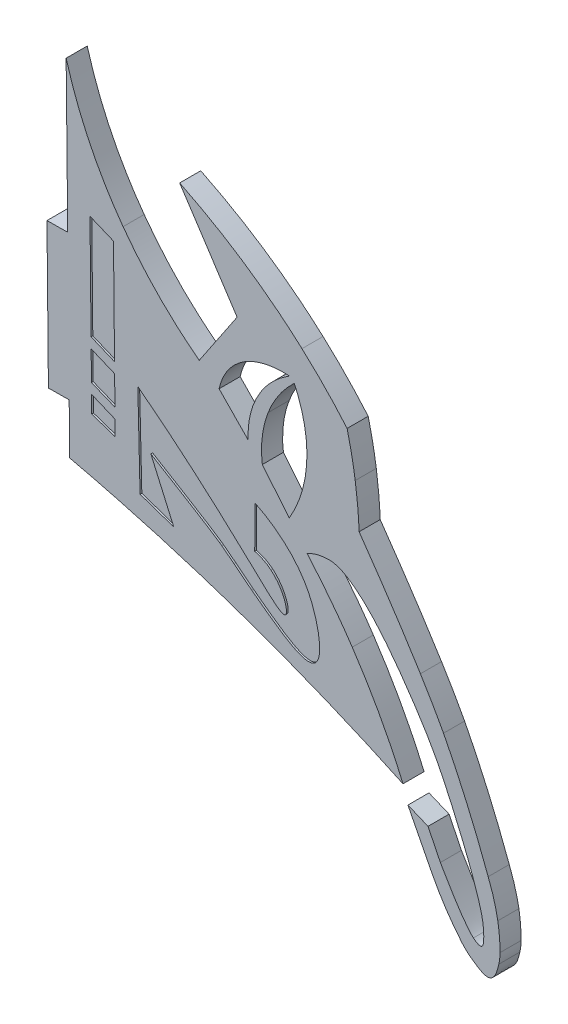
SolidWorks part; units mm, degrees
ref_plane "Front Plane" through (0, 0, 0) normal (0, 0, 1) x (1, 0, 0)
ref_plane "Top Plane" through (0, 0, 0) normal (0, 1, 0) x (1, 0, 0)
ref_plane "Right Plane" through (0, 0, 0) normal (1, 0, 0) x (0, 0, -1)
sketch "Model" plane through (0, 0, 0) normal (0, 0, 1) x (1, 0, 0)
  arc A0 (109.8342, 17.7446) -> (118.3605, 4.9282) centre (172.0028, 49.8589) ccw
  spline S0 degree 3 poles (89.0495, 91.6661) (92.4414, 86.8306) (99.9148, 76.0538) (106.5067, 65.3818) knots 0 0 0 0 1 1 1 1
  spline S1 degree 3 poles (106.5067, 65.3818) (108.7494, 61.7509) (110.6486, 58.5278) (113.0808, 54.0033) knots 0 0 0 0 1 1 1 1
  spline S2 degree 3 poles (113.0808, 54.0033) (113.0808, 54.0033) (119.4156, 42.2191) (125.7952, 24.9855) knots 0 0 0 0 1 1 1 1
  spline S3 degree 3 poles (125.7952, 24.9855) (127.3076, 21.1773) (128.0996, 17.9039) (128.5407, 15.4913) knots 0 0 0 0 1 1 1 1
  spline S4 degree 3 poles (128.5407, 15.4913) (128.6328, 14.9875) (129.1911, 11.8493) (129.1467, 7.9287) knots 0 0 0 0 1 1 1 1
  spline S5 degree 3 poles (129.1467, 7.9287) (129.1363, 7.0034) (129.0927, 6.073) (128.823, 4.9282) knots 0 0 0 0 1 1 1 1
  spline S6 degree 3 poles (128.823, 4.9282) (128.4803, 3.4737) (127.8969, 0.9606) (126.4403, 0.3327) knots 0 0 0 0 1 1 1 1
  spline S7 degree 3 poles (126.4403, 0.3327) (124.9863, -0.2941) (123.1069, 1.0387) (121.4636, 2.1551) knots 0 0 0 0 1 1 1 1
  spline S8 degree 3 poles (121.4636, 2.1551) (119.5407, 3.4615) (118.425, 4.8435) (118.2434, 5.0722) knots 0 0 0 0 1 1 1 1
  spline S9 degree 3 poles (109.8342, 17.7446) (106.7356, 23.7431) (104.3359, 28.4679) (102.9408, 31.2257) knots 0 0 0 0 1 1 1 1
  spline S10 degree 3 poles (102.9408, 31.2257) (104.8481, 30.431) (106.7554, 29.6364) (108.6627, 28.8417) knots 0 0 0 0 1 1 1 1
  spline S11 degree 3 poles (108.6627, 28.8417) (110.2423, 25.6899) (111.4556, 23.1835) (112.1799, 21.6746) knots 0 0 0 0 1 1 1 1
  spline S12 degree 3 poles (112.1799, 21.6746) (113.8081, 18.8225) (118.9735, 9.9101) (121.5951, 7.7916) knots 0 0 0 0 1 1 1 1
  spline S13 degree 3 poles (121.5951, 7.7916) (122.0493, 7.4245) (123.1617, 6.5256) (123.8573, 6.8378) knots 0 0 0 0 1 1 1 1
  spline S14 degree 3 poles (123.8573, 6.8378) (124.2901, 7.032) (124.3894, 7.6178) (124.4342, 7.9593) knots 0 0 0 0 1 1 1 1
  spline S15 degree 3 poles (124.4342, 7.9593) (124.8453, 11.0893) (123.9943, 14.5401) (123.7162, 15.5897) knots 0 0 0 0 1 1 1 1
  spline S16 degree 3 poles (123.7162, 15.5897) (123.4064, 16.759) (123.1307, 17.6908) (122.943, 18.3066) knots 0 0 0 0 1 1 1 1
  spline S17 degree 3 poles (122.943, 18.3066) (122.4308, 19.9867) (121.9247, 21.3933) (121.2666, 23.2106) knots 0 0 0 0 1 1 1 1
  spline S18 degree 3 poles (121.2666, 23.2106) (120.2266, 26.0828) (119.3492, 28.2202) (118.5171, 30.2527) knots 0 0 0 0 1 1 1 1
  spline S19 degree 3 poles (118.5171, 30.2527) (117.0889, 33.7411) (115.9016, 36.3982) (115.3829, 37.5462) knots 0 0 0 0 1 1 1 1
  spline S20 degree 3 poles (115.3829, 37.5462) (113.7377, 41.1877) (112.1337, 44.5392) (111.0619, 46.5479) knots 0 0 0 0 1 1 1 1
  spline S21 degree 3 poles (111.0619, 46.5479) (108.6571, 51.0544) (105.5213, 56.1282) (100.5673, 63.0331) knots 0 0 0 0 1 1 1 1
  spline S22 degree 3 poles (100.5673, 63.0331) (88.4832, 79.8762) (82.5042, 80.4291) (80.6814, 80.473) knots 0 0 0 0 1 1 1 1
  spline S23 degree 3 poles (80.6814, 80.473) (77.988, 80.538) (75.7343, 79.7002) (74.2038, 78.9429) knots 0 0 0 0 1 1 1 1
  spline S24 degree 3 poles (74.2038, 78.9429) (78.4138, 74.1427) (82.8098, 68.5824) (87.0926, 62.2261) knots 0 0 0 0 1 1 1 1
  spline S25 degree 3 poles (87.0926, 62.2261) (93.51, 52.7017) (98.1507, 43.6502) (101.537, 35.7589) knots 0 0 0 0 1 1 1 1
  spline S26 degree 3 poles (101.537, 35.7589) (84.7039, 43.6876) (65.4485, 51.5468) (43.8664, 58.434) knots 0 0 0 0 1 1 1 1
  spline S27 degree 3 poles (43.8664, 58.434) (30.8621, 62.5839) (18.4049, 65.9367) (6.6431, 68.654) knots 0 0 0 0 1 1 1 1
  spline S28 degree 3 poles (6.6431, 68.654) (6.5953, 73.4088) (6.5476, 78.1636) (6.4998, 82.9183) knots 0 0 0 0 1 1 1 1
  spline S29 degree 3 poles (6.4998, 82.9183) (4.529, 82.8985) (2.5583, 82.8787) (0.5875, 82.8588) knots 0 0 0 0 1 1 1 1
  spline S30 degree 3 poles (0.5875, 82.8588) (0.4499, 96.5605) (0.3122, 110.2622) (0.1745, 123.9638) knots 0 0 0 0 1 1 1 1
  spline S31 degree 3 poles (0.1745, 123.9638) (2.1453, 123.9836) (4.1161, 124.0035) (6.0868, 124.0233) knots 0 0 0 0 1 1 1 1
  spline S32 degree 3 poles (6.0868, 124.0233) (5.9349, 138.2581) (5.783, 152.493) (5.631, 166.7278) knots 0 0 0 0 1 1 1 1
  spline S33 degree 3 poles (5.631, 166.7278) (7.986, 158.407) (12.5683, 146.0618) (21.8466, 133.2893) knots 0 0 0 0 1 1 1 1
  spline S34 degree 3 poles (21.8466, 133.2893) (29.3171, 123.0052) (37.3585, 115.849) (43.5353, 111.1676) knots 0 0 0 0 1 1 1 1
  spline S35 degree 3 poles (43.5353, 111.1676) (47.1256, 116.514) (50.7159, 121.8605) (54.3062, 127.2069) knots 0 0 0 0 1 1 1 1
  spline S36 degree 3 poles (54.3062, 127.2069) (48.8561, 135.5143) (43.4061, 143.8216) (37.9559, 152.129) knots 0 0 0 0 1 1 1 1
  spline S37 degree 3 poles (37.9559, 152.129) (48.2244, 147.0975) (60.6363, 139.6523) (72.7766, 128.6746) knots 0 0 0 0 1 1 1 1
  spline S38 degree 3 poles (72.7766, 128.6746) (77.7484, 124.1788) (82.0021, 119.6988) (85.6305, 115.4366) knots 0 0 0 0 1 1 1 1
  spline S39 degree 3 poles (85.6305, 115.4366) (86.5169, 111.8913) (87.3202, 107.981) (87.9344, 103.7405) knots 0 0 0 0 1 1 1 1
  spline S40 degree 3 poles (87.9344, 103.7405) (88.5613, 99.4122) (88.9003, 95.3665) (89.0495, 91.6661) knots 0 0 0 0 1 1 1 1
  spline S41 degree 3 poles (57.477, 98.4752) (54.71, 101.3103) (51.9429, 104.1454) (49.1759, 106.9805) knots 0 0 0 0 1 1 1 1
  spline S42 degree 3 poles (49.1759, 106.9805) (49.5452, 108.7153) (50.5286, 111.9765) (53.436, 114.9068) knots 0 0 0 0 1 1 1 1
  spline S43 degree 3 poles (53.436, 114.9068) (59.3502, 120.8674) (68.0369, 120.2285) (69.1853, 120.1266) knots 0 0 0 0 1 1 1 1
  spline S44 degree 3 poles (69.1853, 120.1266) (67.1601, 118.8788) (63.696, 116.3783) (61.0169, 112.1303) knots 0 0 0 0 1 1 1 1
  spline S45 degree 3 poles (61.0169, 112.1303) (57.3739, 106.3538) (57.3471, 100.7781) (57.477, 98.4752) knots 0 0 0 0 1 1 1 1
  spline S46 degree 3 poles (70.5876, 119.0364) (68.5981, 117.1749) (65.2564, 113.561) (63.1444, 108.1027) knots 0 0 0 0 1 1 1 1
  spline S47 degree 3 poles (63.1444, 108.1027) (60.8676, 102.2184) (61.1485, 97.1068) (61.4925, 94.4665) knots 0 0 0 0 1 1 1 1
  spline S48 degree 3 poles (61.4925, 94.4665) (64.0416, 91.3429) (66.5906, 88.2193) (69.1397, 85.0957) knots 0 0 0 0 1 1 1 1
  spline S49 degree 3 poles (69.1397, 85.0957) (70.8149, 87.9311) (72.7786, 92.086) (73.6876, 97.35) knots 0 0 0 0 1 1 1 1
  spline S50 degree 3 poles (73.6876, 97.35) (75.4164, 107.3623) (72.2966, 115.4064) (70.5876, 119.0364) knots 0 0 0 0 1 1 1 1
  spline S51 degree 3 poles (19.1134, 128.36) (16.8845, 129.2885) (14.6557, 130.217) (12.4268, 131.1454) knots 0 0 0 0 1 1 1 1
  spline S52 degree 3 poles (12.4268, 131.1454) (12.5258, 121.288) (12.6249, 111.4305) (12.7239, 101.573) knots 0 0 0 0 1 1 1 1
  spline S53 degree 3 poles (12.7239, 101.573) (14.9527, 100.6445) (17.1816, 99.716) (19.4105, 98.7876) knots 0 0 0 0 1 1 1 1
  spline S54 degree 3 poles (19.4105, 98.7876) (19.3114, 108.645) (19.2124, 118.5025) (19.1134, 128.36) knots 0 0 0 0 1 1 1 1
  spline S55 degree 3 poles (19.4402, 95.8303) (17.2113, 96.7588) (14.9825, 97.6873) (12.7536, 98.6158) knots 0 0 0 0 1 1 1 1
  spline S56 degree 3 poles (12.7536, 98.6158) (12.7813, 95.8553) (12.8091, 93.0949) (12.8368, 90.3345) knots 0 0 0 0 1 1 1 1
  spline S57 degree 3 poles (12.8368, 90.3345) (15.0653, 89.4366) (17.2939, 88.5388) (19.5225, 87.641) knots 0 0 0 0 1 1 1 1
  spline S58 degree 3 poles (19.5225, 87.641) (19.495, 90.3708) (19.4676, 93.1006) (19.4402, 95.8303) knots 0 0 0 0 1 1 1 1
  spline S59 degree 3 poles (19.5522, 84.6838) (17.3233, 85.6123) (15.0944, 86.5408) (12.8656, 87.4692) knots 0 0 0 0 1 1 1 1
  spline S60 degree 3 poles (12.8656, 87.4692) (12.8818, 85.853) (12.8981, 84.2368) (12.9143, 82.6206) knots 0 0 0 0 1 1 1 1
  spline S61 degree 3 poles (12.9143, 82.6206) (15.1414, 81.8693) (17.3685, 81.118) (19.5955, 80.3668) knots 0 0 0 0 1 1 1 1
  spline S62 degree 3 poles (19.5955, 80.3668) (19.5811, 81.8058) (19.5666, 83.2448) (19.5522, 84.6838) knots 0 0 0 0 1 1 1 1
  spline S63 degree 3 poles (59.331, 71.9865) (59.3378, 75.9743) (59.3446, 79.962) (59.3514, 83.9498) knots 0 0 0 0 1 1 1 1
  spline S64 degree 3 poles (59.3514, 83.9498) (63.011, 82.1678) (71.5847, 77.3339) (75.5479, 67.5052) knots 0 0 0 0 1 1 1 1
  spline S65 degree 3 poles (75.5479, 67.5052) (77.3708, 62.9844) (79.2426, 54.8664) (76.2574, 52.8752) knots 0 0 0 0 1 1 1 1
  spline S66 degree 3 poles (76.2574, 52.8752) (73.2198, 50.849) (65.8813, 56.3911) (58.4471, 61.9849) knots 0 0 0 0 1 1 1 1
  spline S67 degree 3 poles (58.4471, 61.9849) (56.472, 63.4711) (55.4619, 64.3578) (53.3995, 65.9936) knots 0 0 0 0 1 1 1 1
  spline S68 degree 3 poles (53.3995, 65.9936) (51.8899, 67.191) (50.6203, 68.1567) (49.9345, 68.674) knots 0 0 0 0 1 1 1 1
  spline S69 degree 3 poles (49.9345, 68.674) (49.9345, 68.674) (49.6701, 68.8735) (49.411, 69.0675) knots 0 0 0 0 1 1 1 1
  spline S70 degree 3 poles (49.411, 69.0675) (47.927, 70.179) (40.2873, 74.9071) (29.754, 81.2124) knots 0 0 0 0 1 1 1 1
  spline S71 degree 3 poles (29.754, 81.2124) (31.9284, 76.2927) (34.1028, 71.373) (36.2773, 66.4532) knots 0 0 0 0 1 1 1 1
  spline S72 degree 3 poles (36.2773, 66.4532) (33.0788, 67.547) (29.8803, 68.6407) (26.6818, 69.7345) knots 0 0 0 0 1 1 1 1
  spline S73 degree 3 poles (26.6818, 69.7345) (26.4688, 78.4896) (26.2559, 87.2448) (26.0429, 95.9999) knots 0 0 0 0 1 1 1 1
  spline S74 degree 3 poles (26.0429, 95.9999) (31.7263, 91.6154) (39.7647, 85.159) (49.017, 76.8087) knots 0 0 0 0 1 1 1 1
  spline S75 degree 3 poles (49.017, 76.8087) (61.1068, 65.8974) (66.5679, 59.6054) (68.0228, 60.6739) knots 0 0 0 0 1 1 1 1
  spline S76 degree 3 poles (68.0228, 60.6739) (69.1104, 61.4726) (67.5557, 66.6505) (63.9952, 69.6408) knots 0 0 0 0 1 1 1 1
  spline S77 degree 3 poles (63.9952, 69.6408) (62.3467, 71.0254) (60.5942, 71.6681) (59.331, 71.9865) knots 0 0 0 0 1 1 1 1
extrude "Boss-Extrude1" add sketch "Model" along normal blind 5.5 contours S40 S39 S38 S37 S36 S35 S34 S33 S32 S31 S30 S29 S28 S27 S26 S25 S24 S23 S22 S21 S20 S19 S18 S17 S16 S15 S14 S13 S12 S11 S10 S9 A0 S8 S7 S6 S5 S4 S3 S2 S1 S0 S62 S61 S60 S59 S58 | S53 S54 S51 S52 | S61 S62 S59 S60 | S57 S58 S55 S56 | S77 S76 S75 S74 S73 S72 S71 S70 S69 S68 S67 S66 S65 S64 S63 region at (53.6049, 89.3028, 0) region at (15.9186, 114.9665, 0) region at (16.132, 93.1079, 0) region at (16.1673, 83.8094, 0) region at (52.0965, 72.8289, 0)
extrude "Boss-Extrude2" add sketch "Model<3>" along normal blind 6 contours S40 S39 S38 S37 S36 S35 S34 S33 S32 S31 S30 S29 S28 S27 S26 S25 S24 S23 S22 S21 S20 S19 S18 S17 S16 S15 S14 S13 S12 S11 S10 S9 A0 S8 S7 S6 S5 S4 S3 S2 S1 S0 S62 S61 S60 S59 S58 region at (53.6049, 89.3028, 0)
sketch "Model<3>" plane through (0, 0, 0) normal (0, 0, 1) x (1, 0, 0) same geometry as "Model"
